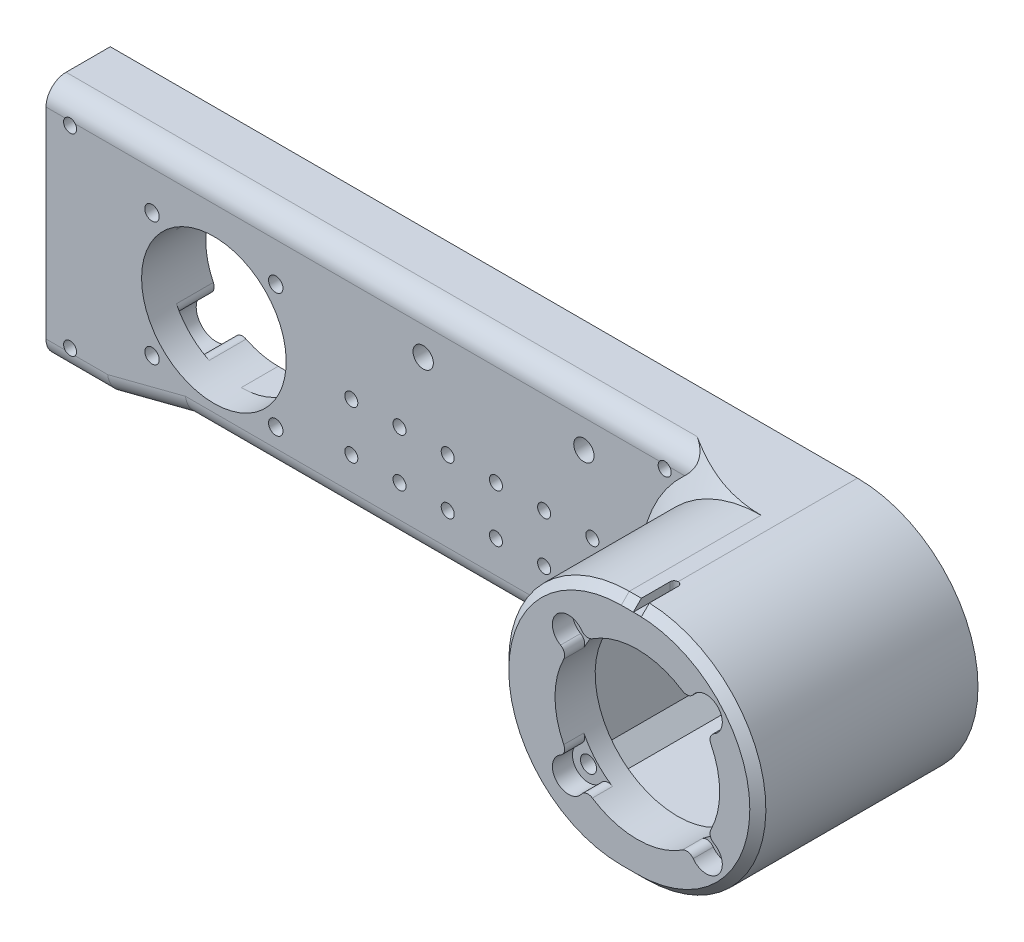
SolidWorks part; units mm, degrees
ref_plane "前视基准面" through (0, 0, 0) normal (0, 0, 1) x (1, 0, 0)
ref_plane "上视基准面" through (0, 0, 0) normal (0, 1, 0) x (1, 0, 0)
ref_plane "右视基准面" through (0, 0, 0) normal (1, 0, 0) x (0, 0, -1)
other "Configuration Table"
sketch "草图1" plane through (0, 0, 0) normal (0, 0, 1) x (1, 0, 0)
  line L0 (0, 0) -> (-18.5134, 0) construction
  line L1 (-2, 15) -> (0, 15)
  line L2 (-2, -15) -> (0, -15)
  arc A0 (0, -15) -> (0, 15) centre (0, 0) ccw
  circle A1 centre (0, 0) radius 10.25
  arc A2 (-2, 15) -> (-2, -15) centre (-2, 0) ccw
  dimension "D1" = 30
  dimension "D2" = 20.5
  dimension "D3" = 30
  dimension "D4" = 2
extrude "凸台-拉伸1" add sketch "草图1" along normal blind 27.4
sketch "草图2" plane through (0, 0, 0) normal (0, 0, -1) x (-1, 0, 0)
  line L0 (2, 15) -> (93, 15)
  line L1 (93, 15) -> (93, -15.0038)
  line L2 (93, -15.0038) -> (85, -15.0038)
  line L3 (85, -15.0038) -> (75.3185, -12.5)
  line L4 (75.3185, -12.5) -> (31.6825, -12.5)
  line L5 (31.6825, -12.5) -> (22, -15)
  line L6 (22, -15) -> (2, -15)
  arc A0 (2, -15) -> (2, 15) centre (2, 0) ccw construction
  arc A1 (2, -15) -> (2, 15) centre (2, 0) ccw
  dimension "D1" = 91
  dimension "D2" = 8
  dimension "D3" = 14.5
  dimension "D4" = 2.5
  dimension "D5" = 10
  dimension "D6" = 10
  dimension "D7" = 20
extrude "凸台-拉伸2" add sketch "草图2" against normal blind 8
sketch "草图3" plane through (0, 0, 0) normal (0, 0, -1) x (-1, 0, 0)
  line L0 (-10.7, 8.636) -> (-8.636, 10.7)
  line L1 (8.636, -10.7) -> (-8.636, -10.7)
  line L2 (10.7, -8.636) -> (10.7, 8.636)
  line L3 (8.636, 10.7) -> (-8.636, 10.7)
  line L4 (-10.7, -8.636) -> (-10.7, 8.636)
  line L5 (10.7, -10.7) -> (-10.7, 10.7) construction
  line L6 (10.7, 10.7) -> (-10.7, -10.7) construction
  line L7 (10.7, 8.636) -> (8.636, 10.7)
  line L8 (8.636, -10.7) -> (10.7, -8.636)
  line L9 (-8.636, -10.7) -> (-10.7, -8.636)
  point P0 (0, 0)
  dimension "D1" = 21.4
  dimension "D2" = 21.4
extrude "切除-拉伸1" cut sketch "草图3" against normal blind 22.4
sketch "草图4" plane through (0, 0, 0) normal (0, 0, -1) x (-1, 0, 0)
  line L0 (0, 0) -> (96.7715, 0) construction
  circle A0 centre (72.105, 0) radius 9
  dimension "D2" = 18
  dimension "D1" = 72.105
extrude "切除-拉伸2" cut sketch "草图4" against normal up to next and the other way through all
sketch "草图5" plane through (0, 0, 0) normal (0, 0, -1) x (-1, 0, 0)
  line L0 (0, 0) -> (76.585, 0) construction
  line L1 (10.336, 9) -> (21.84, 9)
  line L2 (10.7, 8.636) -> (8.636, 10.7) construction
  line L3 (21.84, 9) -> (21.84, 11)
  line L4 (23.84, 13) -> (47.84, 13)
  line L5 (49.84, 11) -> (49.84, 9)
  line L6 (49.84, 9) -> (72.105, 9)
  line L7 (72.105, -9) -> (10.336, -9)
  line L8 (8.636, -10.7) -> (10.7, -8.636) construction
  line L9 (10.7, -8.636) -> (10.7, 8.636) construction
  line L10 (10.7, -8.636) -> (10.7, 8.636)
  line L12 (10.7, 8.636) -> (10.336, 9)
  line L13 (10.7, -8.636) -> (10.336, -9)
  circle A0 centre (72.105, 0) radius 9 construction
  arc A1 (72.105, -9) -> (72.105, 9) centre (72.105, 0) ccw
  arc A2 (49.84, 11) -> (47.84, 13) centre (47.84, 11) ccw
  arc A3 (23.84, 13) -> (21.84, 11) centre (23.84, 11) ccw
  point P20 (49.84, 13)
  point P23 (21.84, 13)
  dimension "D4" = 2
  dimension "D1" = 11.14
  dimension "D2" = 28
  dimension "D3" = 13
extrude "切除-拉伸3" cut sketch "草图5" against normal blind 4.6
sketch "草图6" plane through (0, 0, 0) normal (0, 0, -1) x (-1, 0, 0)
  line L1 (79.805, -7.7) -> (64.405, -7.7) construction
  line L2 (79.805, -7.7) -> (79.805, 7.7) construction
  line L3 (79.805, 7.7) -> (64.405, 7.7) construction
  line L4 (64.405, -7.7) -> (64.405, 7.7) construction
  line L5 (79.805, -7.7) -> (64.405, 7.7) construction
  line L6 (79.805, 7.7) -> (64.405, -7.7) construction
  circle A0 centre (64.405, 7.7) radius 2.5
  circle A1 centre (79.805, 7.7) radius 2.5
  circle A2 centre (79.805, -7.7) radius 2.5
  circle A3 centre (64.405, -7.7) radius 2.5
  point P0 (72.105, 0)
  dimension "D3" = 5
  dimension "D1" = 15.4
  dimension "D2" = 15.4
extrude "切除-拉伸4" cut sketch "草图6" against normal up to surface (4.6 mm away) up to face at (-32.6935, 5.569, 4.6)
sketch "草图7" plane through (0, 0, 4.6) normal (0, 0, -1) x (-1, 0, 0)
  circle A0 centre (64.405, 7.7) radius 0.9
  circle A1 centre (79.805, 7.7) radius 0.9
  circle A2 centre (64.405, -7.7) radius 0.9
  circle A3 centre (79.805, -7.7) radius 0.9
  dimension "D1" = 1.8
extrude "切除-拉伸5" cut sketch "草图7" against normal up to next
fillet "圆角1" radius 1 8 edges at (-62.2696, -9, 2.3) (-66.5404, -9, 2.3) (-77.3332, -7.3257, 2.3) (-79.4307, -5.2282, 2.3) (-79.4307, 5.2282, 2.3) (-77.3332, 7.3257, 2.3) (-66.5404, 9, 2.3) (-62.2696, 9, 2.3)
sketch "草图8" plane through (0, 0, 4.6) normal (0, 0, -1) x (-1, 0, 0)
  line L0 (0, 0) -> (97.2138, 0) construction
  line L1 (25, 0) -> (31, 0) construction
  line L2 (25, 0) -> (25, -6) construction
  circle A2 centre (25, 0) radius 0.8115
  circle A3 centre (31, 0) radius 0.8115
  circle A4 centre (37, 0) radius 0.8115
  circle A5 centre (43, 0) radius 0.8115
  circle A6 centre (49, 0) radius 0.8115
  circle A7 centre (55, 0) radius 0.8115
  circle A8 centre (31, -6) radius 0.8115
  circle A9 centre (37, -6) radius 0.8115
  circle A10 centre (43, -6) radius 0.8115
  circle A11 centre (49, -6) radius 0.8115
  circle A12 centre (55, -6) radius 0.8115
  circle A13 centre (25, -6) radius 0.8115
  dimension "D1" = 1.623
  dimension "D2" = 25
  dimension "D4" = 6
  dimension "D5" = 6
  dimension "D3" = 6
extrude "切除-拉伸6" cut sketch "草图8" against normal up to next
sketch "草图9" plane through (0, 0, 4.6) normal (0, 0, -1) x (-1, 0, 0)
  line L0 (0, 0) -> (57.5971, 0) construction
  line L1 (21.84, 11) -> (21.84, 9) construction
  circle A0 centre (26.053, 9) radius 1.2645
  circle A1 centre (46.053, 9) radius 1.2645
  dimension "D2" = 2.529
  dimension "D3" = 20
  dimension "D4" = 4.213
  dimension "D1" = 9
extrude "切除-拉伸7" cut sketch "草图9" against normal up to next
sketch "草图10" plane through (0, 0, 0) normal (0, 0, -1) x (-1, 0, 0)
  line L0 (0, 0) -> (98.5421, 0) construction
  line L1 (93, -15.0038) -> (93, 15) construction
  circle A0 centre (16, 12) radius 0.8115
  circle A1 centre (16, -12) radius 0.8115
  circle A2 centre (90, 12) radius 0.8115
  circle A3 centre (90, -12) radius 0.8115
  dimension "D1" = 1.623
  dimension "D3" = 24
  dimension "D4" = 3
  dimension "D5" = 24
  dimension "D2" = 16
extrude "切除-拉伸8" cut sketch "草图10" against normal up to next
hole_wizard "孔1" positions "草图12" profile "草图13" legacy end condition up to next
sketch "草图12" plane through (0, 0, 27.4) normal (0, 0, 1) x (1, 0, 0)
  line L1 (-8.5739, 7.6641) -> (8.5739, 7.6641) construction
  line L2 (-8.5739, 7.6641) -> (-8.5739, -7.6641) construction
  line L3 (-8.5739, -7.6641) -> (8.5739, -7.6641) construction
  line L4 (8.5739, 7.6641) -> (8.5739, -7.6641) construction
  circle A0 centre (0, 0) radius 11.5 construction
  point P4 (-8.5739, 7.6641)
  point P5 (8.5739, -7.6641)
  point P224 (-8.5739, -7.6641)
  point P225 (8.5739, 7.6641)
  point P230 (-8.5739, 7.6641)
  point P234 (8.5739, 7.6641)
  point P238 (8.5739, -7.6641)
  point P242 (-8.5739, -7.6641)
  dimension "D1" = 23
sketch "草图13" plane through (-8.5739, -7.6641, 27.4) normal (1, 0, 0) x (0, -1, 0)
  line L0 (0, 0) -> (0, 5)
  line L1 (0, 5) -> (1, 5)
  line L2 (1, 5) -> (1, 2.5)
  line L3 (1, 2.5) -> (2, 2.5)
  line L4 (2, 2.5) -> (2, 0)
  line L5 (2, 0) -> (0, 0)
  line L6 (0, 110) -> (0, -10) construction
  dimension "直径" = 2
  dimension "深度" = 5
  dimension "柱坑直径" = 4
  dimension "柱坑深度" = 2.5
fillet "圆角2" radius 1 8 edges at (6.5832, -7.8565, 26.15) (8.5427, -5.6643, 26.15) (-8.5427, -5.6643, 26.15) (-6.5832, -7.8565, 26.15) (8.5427, 5.6643, 26.15) (6.5832, 7.8565, 26.15) (-6.5832, 7.8565, 26.15) (-8.5427, 5.6643, 26.15)
chamfer "倒角1" distance 1 angle 45 4 edges at (15, 0, 27.4) (-1, 15, 27.4) (-1, -15, 27.4) (-17, 0, 27.4)
chamfer "倒角2" distance 2 angle 45 1 edges at (-17, 0, 8)
fillet "圆角3" radius 2.5 6 edges at (-51.5, 15, 8) (-16, -15, 8) (-26.8412, -13.75, 8) (-53.5005, -12.5, 8) (-80.1593, -13.7519, 8) (-89, -15.0038, 8)
ref_plane "基准面1" through (0, 15, 0) normal (0, 1, 0) x (1, 0, 0)
sketch "草图14" plane through (0, 15, 0) normal (0, 1, 0) x (1, 0, 0)
  line L0 (0, -27.4) -> (0, -22.823) construction
  line L1 (0, -26.4) -> (0, 0) construction
  line L2 (-0.5, -27.4) -> (-0.5, -22.823)
  line L3 (0.5, -27.4) -> (0.5, -22.823)
  arc A0 (-0.5, -27.4) -> (0.5, -27.4) centre (0, -27.4) ccw
  arc A1 (0.5, -22.823) -> (-0.5, -22.823) centre (0, -22.823) ccw
  point P5 (0, -25.1115)
  dimension "D1" = 1
  dimension "D2" = 4.577
extrude "切除-拉伸9" cut sketch "草图14" against normal blind 1
sketch "草图15" plane through (-93, 0, 0) normal (-1, 0, 0) x (0, 0, 1)
  line L0 (0, 0) -> (9.3963, 0) construction
  line L1 (0, -15.0038) -> (0, 15) construction
  circle A0 centre (4.6, 12) radius 1.25
  circle A2 centre (4.6, -12) radius 1.25
  dimension "D1" = 2.5
  dimension "D2" = 24
  dimension "D3" = 4.6
extrude "切除-拉伸10" cut sketch "草图15" against normal blind 1.2
chamfer "倒角3" distance 0.2 angle 45 2 edges at (-93, -12, 3.35) (-93, 12, 5.85)
sketch "草图16" plane through (-93, 0, 0) normal (-1, 0, 0) x (0, 0, 1)
  line L0 (0, 0) -> (8.6656, 0) construction
  line L1 (0, -15.0038) -> (0, 15) construction
  circle A0 centre (4.6, 7) radius 1.2645
  circle A1 centre (4.6, -7) radius 1.2645
  dimension "D1" = 2.529
  dimension "D3" = 14
  dimension "D2" = 4.6
extrude "切除-拉伸11" cut sketch "草图16" against normal blind 4.8
